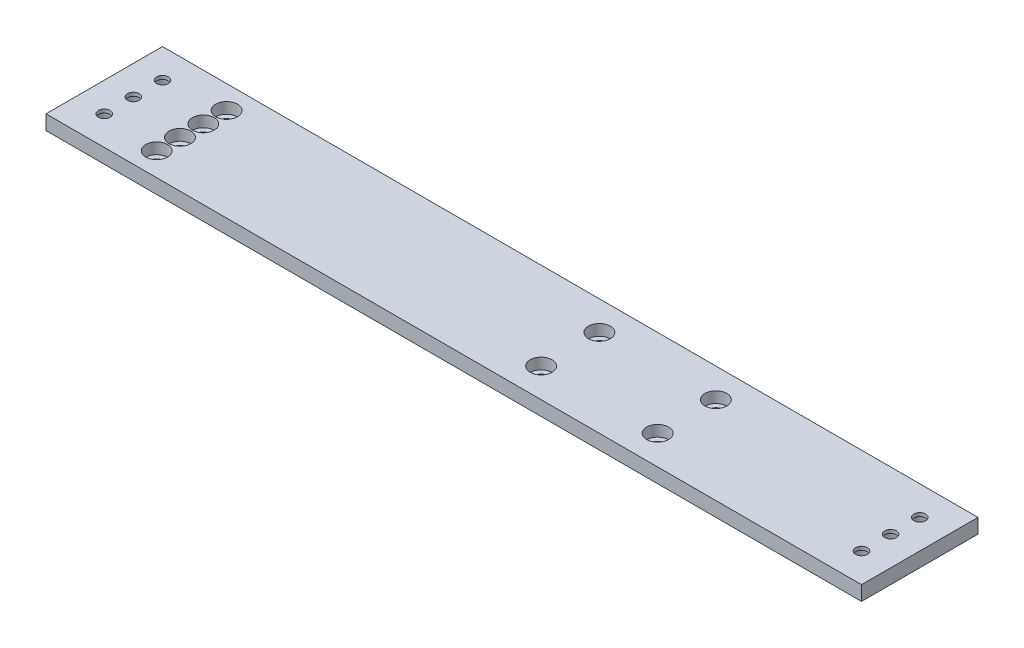
SolidWorks part; units mm, degrees
material "6061-T6 (SS)"
ref_plane "Front" through (0, 0, 0) normal (0, 0, 1) x (1, 0, 0)
ref_plane "Top" through (0, 0, 0) normal (0, 1, 0) x (1, 0, 0)
ref_plane "Right" through (0, 0, 0) normal (1, 0, 0) x (0, 0, -1)
sketch "Sketch1" plane through (0, 0, 0) normal (0, 1, 0) x (1, 0, 0)
  line L1 (-177.8, -25.4) -> (177.8, -25.4)
  line L2 (-177.8, -25.4) -> (-177.8, 25.4)
  line L3 (-177.8, 25.4) -> (177.8, 25.4)
  line L4 (177.8, -25.4) -> (177.8, 25.4)
  line L5 (-177.8, -25.4) -> (177.8, 25.4) construction
  line L6 (-177.8, 25.4) -> (177.8, -25.4) construction
  point P0 (0, 0)
  dimension "D1" = 50.8
  dimension "D2" = 355.6
extrude "Boss-Extrude1" add sketch "Sketch1" along normal blind 6.35
hole_wizard "CBORE for #10 Socket Head Cap Screw1" positions "Sketch2" profile "Sketch4" counterbore size "#10" standard "ANSI Inch" end condition through all
sketch "Sketch2" plane through (0, 6.35, 0) normal (0, 1, 0) x (1, 0, 0)
  line L2 (177.8, 25.4) -> (-177.8, 25.4) construction
  line L6 (-177.8, -25.4) -> (177.8, -25.4) construction
  line L8 (-177.8, 25.4) -> (-177.8, -25.4) construction
  line L12 (177.8, -25.4) -> (177.8, 25.4) construction
  line L15 (25.4, 12.7) -> (25.4, 25.4) construction
  line L17 (25.4, -12.7) -> (25.4, -25.4) construction
  line L18 (-139.7, -25.4) -> (-139.7, -15.24) construction
  line L20 (-139.7, 5.08) -> (-139.7, 15.24) construction
  line L21 (-139.7, 15.24) -> (-139.7, 25.4) construction
  line L22 (-139.7, 5.08) -> (-139.7, -5.08) construction
  line L23 (-139.7, -5.08) -> (-139.7, -15.24) construction
  point P64 (25.4, 12.7)
  point P66 (76.2, 12.7)
  point P68 (25.4, -12.7)
  point P70 (76.2, -12.7)
  point P92 (-139.7, 15.24)
  point P94 (-139.7, 5.08)
  point P102 (-139.7, -15.24)
  point P127 (-139.7, -5.08)
  dimension "D2" = 50.8
  dimension "D3" = 25.4
  dimension "D4" = 101.6
  dimension "D5" = 38.1
sketch "Sketch4" plane through (-139.7, 6.35, 5.08) normal (1, 0, 0) x (0, 0, 1)
  line L0 (0, 0) -> (0, 6.35)
  line L1 (0, 6.35) -> (2.5527, 6.35)
  line L3 (2.5527, 6.35) -> (2.5527, 4.826)
  line L4 (2.5527, 4.826) -> (4.7625, 4.826)
  line L5 (4.7625, 4.826) -> (4.7625, 0)
  line L7 (4.7625, 0) -> (0, 0)
  line L11 (0, -6.35) -> (0, 107.95) construction
  dimension "Thru Hole Dia." = 5.1054
  dimension "Thru Hole Depth" = 6.35
  dimension "C'Bore Dia." = 9.525
  dimension "C'Bore Depth" = 4.826
sketch "Sketch7" plane through (0, 0, 0) normal (0, -1, 0) x (1, 0, 0)
  line L0 (-165.1, 25.4) -> (-165.1, 12.7) construction
  line L1 (-177.8, 25.4) -> (177.8, 25.4) construction
  line L2 (-165.1, 12.7) -> (-165.1, 0) construction
  line L3 (-165.1, 0) -> (-165.1, -12.7) construction
  line L4 (-165.1, -12.7) -> (-165.1, -25.4) construction
  line L5 (177.8, -25.4) -> (-177.8, -25.4) construction
  line L7 (-177.8, -25.4) -> (-177.8, 25.4) construction
  line L8 (165.1, 25.4) -> (165.1, 12.7) construction
  line L9 (165.1, 12.7) -> (165.1, 0) construction
  line L10 (165.1, 0) -> (165.1, -12.7) construction
  line L11 (165.1, -12.7) -> (165.1, -25.4) construction
  line L13 (177.8, 25.4) -> (177.8, -25.4) construction
  point P0 (-165.1, 12.7)
  point P2 (-165.1, 0)
  point P4 (-165.1, -12.7)
  point P6 (165.1, 12.7)
  point P8 (165.1, 0)
  point P10 (165.1, -12.7)
  dimension "D1" = 12.7
  dimension "D2" = 12.7
hole_wizard "CBORE for #10 Socket Head Cap Screw2" positions "Sketch7" profile "Sketch6" counterbore size "#10" standard "ANSI Inch" end condition through all
sketch "Sketch6" plane through (-165.1, 0, 12.7) normal (1, 0, 0) x (0, 0, -1)
  line L0 (0, 0) -> (0, 6.35)
  line L1 (0, 6.35) -> (2.5527, 6.35)
  line L3 (2.5527, 6.35) -> (2.5527, 4.826)
  line L4 (2.5527, 4.826) -> (4.7625, 4.826)
  line L5 (4.7625, 4.826) -> (4.7625, 0)
  line L7 (4.7625, 0) -> (0, 0)
  line L11 (0, -6.35) -> (0, 107.95) construction
  dimension "Thru Hole Dia." = 5.1054
  dimension "Thru Hole Depth" = 6.35
  dimension "C'Bore Dia." = 9.525
  dimension "C'Bore Depth" = 4.826
